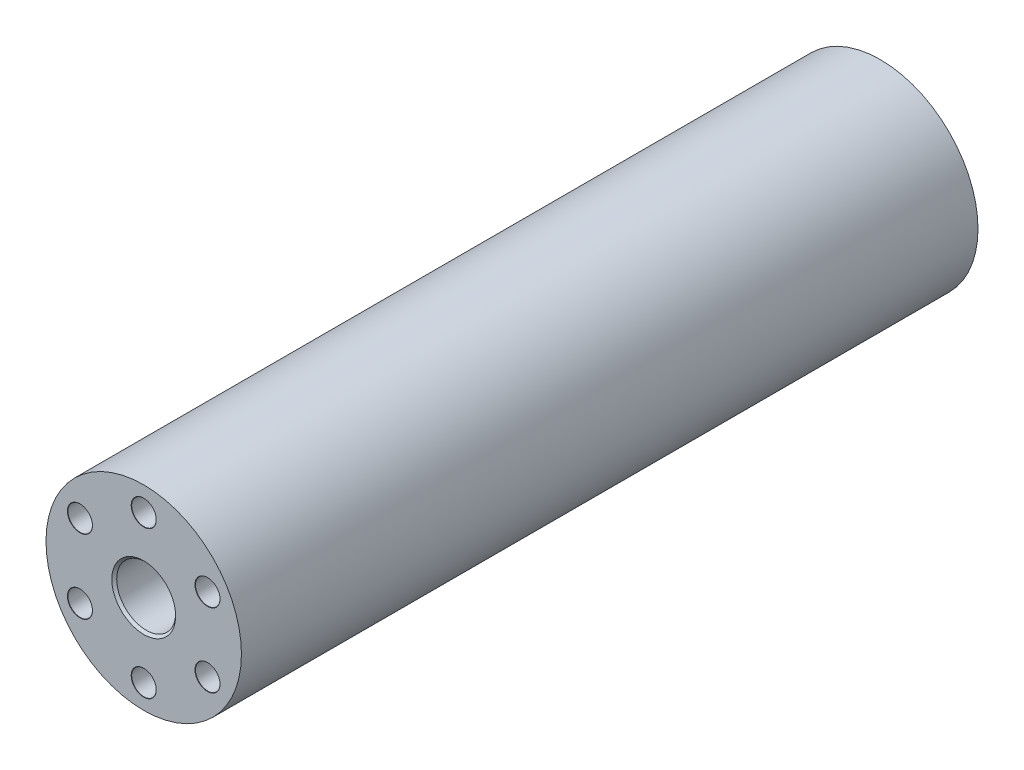
SolidWorks part; units mm, degrees
material "6061-T6 (SS)"
ref_plane "Front Plane" through (0, 0, 0) normal (0, 0, 1) x (1, 0, 0)
ref_plane "Top Plane" through (0, 0, 0) normal (0, 1, 0) x (1, 0, 0)
ref_plane "Right Plane" through (0, 0, 0) normal (1, 0, 0) x (0, 0, -1)
sketch "Sketch1" plane through (0, 0, 0) normal (0, 0, 1) x (1, 0, 0)
  circle A0 centre (0, 0) radius 9.95
  dimension "D1" = 19.9
extrude "Boss-Extrude1" add sketch "Sketch1" along normal blind 75
sketch "Sketch2" plane through (0, 0, 0) normal (0, 0, 1) x (1, 0, 0)
  point P0 (0, 0)
hole_wizard "Ø6.0mm Dowel Hole1" positions "Sketch2" profile "Sketch4" hole size "Ø6.0" standard "DIN" end condition through all
sketch "Sketch4" plane through (0, 0, 0) normal (1, 0, 0) x (0, 1, 0)
  line L0 (0, 0) -> (0, 75)
  line L1 (0, 75) -> (3.25, 75)
  line L2 (3, 74.75) -> (3, 0.25)
  line L3 (3, 0.25) -> (3.25, 0)
  line L5 (3.25, 0) -> (0, 0)
  line L6 (-3, 0.25) -> (-3.25, 0) construction
  line L7 (3.25, 75) -> (3, 74.75)
  line L8 (-3.25, 75) -> (-3, 74.75) construction
  line L11 (0, -6.35) -> (0, 107.95) construction
  dimension "Thru Hole Dia." = 6
  dimension "Thru Hole Depth" = 75
  dimension "Near C'Sink Dia." = 6.5
  dimension "Near C'Sink Angle" = 90
  dimension "Far C'Sink Dia." = 6.5
  dimension "Far C'Sink Angle" = 90
sketch "Sketch5" plane through (0, 0, 0) normal (0, 0, -1) x (-1, 0, 0)
  circle A0 centre (0, 0) radius 7
  point P6 (0, 7)
  point P10 (6.0622, -3.5)
  point P11 (-6.0622, -3.5)
  dimension "D1" = 14
  dimension "D2" = 3
hole_wizard "Tap Drill for M3 Tap1" positions "Sketch5" profile "Sketch6" hole size "M3" standard "DIN"
sketch "Sketch6" plane through (6.0622, -3.5, 0) normal (1, 0, 0) x (0, 1, 0)
  line L0 (0, 0) -> (0, 10.7511)
  line L1 (0, 10.7511) -> (1.25, 10)
  line L2 (1.25, 10) -> (1.25, 0.025)
  line L3 (1.25, 0.025) -> (1.275, 0)
  line L5 (1.275, 0) -> (0, 0)
  line L6 (-1.25, 0.025) -> (-1.275, 0) construction
  line L10 (0, 10.7511) -> (-1.25, 10) construction
  line L11 (0, -6.35) -> (0, 107.95) construction
  dimension "Hole Dia." = 2.5
  dimension "Hole Depth" = 10
  dimension "Near C'Sink Dia." = 2.55
  dimension "Near C'Sink Angle" = 90
  dimension "Drill Angle" = 118
sketch "Sketch7" plane through (0, 0, 75) normal (0, 0, 1) x (1, 0, 0)
  line L0 (0, 3) -> (0, 12) construction
  circle A0 centre (0, 0) radius 3 construction
  circle A2 centre (0, 0) radius 12 construction
  circle A4 centre (0, 0) radius 7.5 construction
  point P20 (0, 7.5)
  point P24 (6.4952, 3.75)
  point P25 (6.4952, -3.75)
  point P26 (0, -7.5)
  point P27 (-6.4952, -3.75)
  point P28 (-6.4952, 3.75)
  dimension "D1" = 15
  dimension "D2" = 6
hole_wizard "Tap Drill for M3 Tap2" positions "Sketch7" profile "Sketch9" hole size "M3" standard "DIN"
sketch "Sketch9" plane through (-6.4952, 3.75, 75) normal (1, 0, 0) x (0, -1, 0)
  line L0 (0, 0) -> (0, 10.7511)
  line L1 (0, 10.7511) -> (1.25, 10)
  line L2 (1.25, 10) -> (1.25, 0.025)
  line L3 (1.25, 0.025) -> (1.275, 0)
  line L5 (1.275, 0) -> (0, 0)
  line L6 (-1.25, 0.025) -> (-1.275, 0) construction
  line L10 (0, 10.7511) -> (-1.25, 10) construction
  line L11 (0, -6.35) -> (0, 107.95) construction
  dimension "Hole Dia." = 2.5
  dimension "Hole Depth" = 10
  dimension "Near C'Sink Dia." = 2.55
  dimension "Near C'Sink Angle" = 90
  dimension "Drill Angle" = 118
